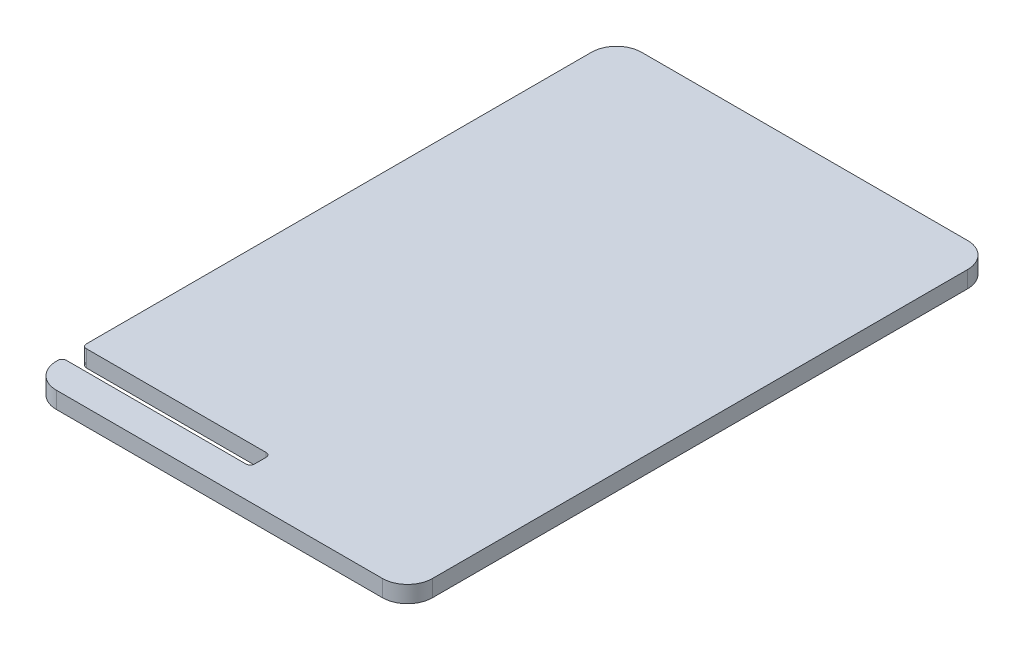
SolidWorks part; units mm, degrees
ref_plane "Alzado" through (0, 0, 0) normal (0, 0, 1) x (1, 0, 0)
ref_plane "Planta" through (0, 0, 0) normal (0, 1, 0) x (1, 0, 0)
ref_plane "Vista lateral" through (0, 0, 0) normal (1, 0, 0) x (0, 0, -1)
sketch "Croquis1" plane through (0, 0, 0) normal (0, 1, 0) x (1, 0, 0)
  line L1 (-22.5, 35.3062) -> (22.5, 35.3062)
  line L2 (-22.5, 35.3062) -> (-22.5, -34.6938)
  line L3 (-22.5, -34.6938) -> (22.5, -34.6938)
  line L4 (22.5, 35.3062) -> (22.5, -34.6938)
  dimension "D1" = 22.5
  dimension "D2" = 45
  dimension "D3" = 35.3062
  dimension "D4" = 70
extrude "Saliente-Extruir1" add sketch "Croquis1" along normal blind 2
sketch "Croquis2" plane through (0, 2, 0) normal (0, 1, 0) x (1, 0, 0)
  line L0 (-22.5, 35.3062) -> (-22.5, -34.6938) construction
  line L1 (-22.5, -28.6) -> (0, -28.6)
  line L2 (-22.5, -28.6) -> (-22.5, -31)
  line L3 (-22.5, -31) -> (0, -31)
  line L4 (0, -28.6) -> (0, -31)
  dimension "D1" = 2.4
  dimension "D2" = 31
  dimension "D3" = 22.5
extrude "Cortar-Extruir1" cut sketch "Croquis2" against normal up to surface (2 mm away) up to face at (0, 0, -0.3062)
fillet "Redondeo1" radius 3 4 edges at (-22.5, 1, 34.6938) (22.5, 1, 34.6938) (-22.5, 1, -35.3062) (22.5, 1, -35.3062)
fillet "Redondeo2" radius 0.5 4 edges at (-22.5, 1, 31) (0, 1, 31) (0, 1, 28.6) (-22.5, 1, 28.6)
